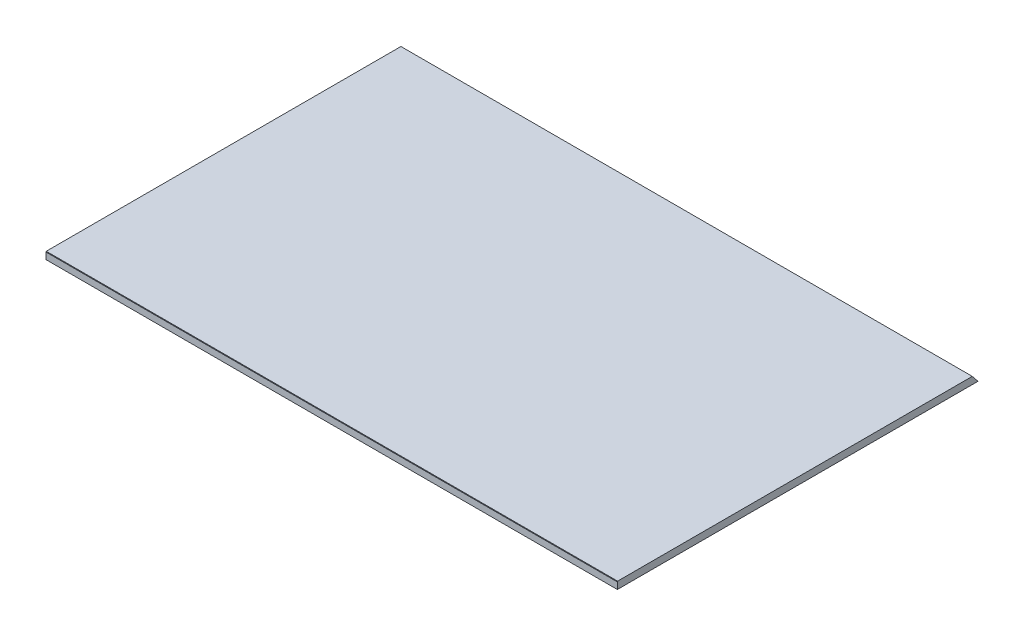
SolidWorks part; units mm, degrees
ref_plane "Front Plane" through (0, 0, 0) normal (0, 0, 1) x (1, 0, 0)
ref_plane "Top Plane" through (0, 0, 0) normal (0, 1, 0) x (1, 0, 0)
ref_plane "Right Plane" through (0, 0, 0) normal (1, 0, 0) x (0, 0, -1)
sketch "Sketch8" plane through (0, 0, 0) normal (1, 0, 0) x (0, 0, -1)
  line L3 (-88.1041, -6) -> (62.8959, -6)
  line L5 (-120, 5.68) -> (-120, 1.9989)
  line L17 (-120, 5.68) -> (-119.856, 6)
  line L25 (-120, 1.9989) -> (-106.1041, -6)
  line L26 (62.8959, -6) -> (80.8959, -3.1767)
  line L27 (-88.1041, -6) -> (-106.1041, -6)
  line L28 (80.9764, -2.9985) -> (82.7813, 0.9991)
  line L29 (80.9764, -2.9985) -> (80.8959, -3.1767)
  line L30 (78.7813, 5.9991) -> (82.7813, 0.9991)
  line L31 (-119.856, 6) -> (78.7813, 5.9991)
  point P0 (0, 0)
  point P6 (0, 0)
  dimension "D1" = 169
extrude "Boss-Extrude2" add sketch "Sketch8" along normal mid plane 320
sketch "Sketch9" plane through (0, 0, 0) normal (0, 0, 1) x (1, 0, 0)
  line L4 (0, 22.1936) -> (0, -18.3739) construction
  line L8 (-160, -6) -> (-142, -6)
  line L9 (160, -6) -> (-160, -6) construction
  line L10 (-160, 1.9989) -> (-160, -6)
  line L11 (-160, 1.9989) -> (-142, -6)
  line L12 (160, -6) -> (142, -6)
  line L13 (160, 1.9989) -> (160, -6)
  line L14 (160, 1.9989) -> (142, -6)
  dimension "D1" = 18
extrude "Cut-Extrude11" cut sketch "Sketch9" against normal through all both and the other way through all
sketch "Sketch12" plane through (0, -6, 0) normal (0, -1, 0) x (1, 0, 0)
  line L0 (-142, -62.8959) -> (-142, 106.1041) construction
  line L1 (-115, -17.8959) -> (118, -17.8959)
  line L2 (-115, -17.8959) -> (-115, -38.8959)
  line L3 (-115, -38.8959) -> (118, -38.8959)
  line L4 (118, -17.8959) -> (118, -38.8959)
  line L5 (-115, -17.8959) -> (118, -38.8959) construction
  line L6 (-115, -38.8959) -> (118, -17.8959) construction
  line L7 (142, 106.1041) -> (-142, 106.1041) construction
  point P0 (1.5, -28.3959)
  dimension "D1" = 233
  dimension "D2" = 21
  dimension "D3" = 27
  dimension "D4" = 124
extrude "Cut-Extrude12" cut sketch "Sketch12" against normal blind 2
sketch "Sketch13" plane through (0, -6, 0) normal (0, -1, 0) x (1, 0, 0)
  line L0 (142, 106.1041) -> (-142, 106.1041) construction
  line L1 (-140, 104.1041) -> (-133, 104.1041)
  line L2 (-140, 104.1041) -> (-140, 81.1041)
  line L3 (-140, 81.1041) -> (-133, 81.1041)
  line L4 (-133, 104.1041) -> (-133, 81.1041)
  line L5 (-140, 104.1041) -> (-133, 81.1041) construction
  line L6 (-140, 81.1041) -> (-133, 104.1041) construction
  line L7 (-142, -62.8959) -> (-142, 106.1041) construction
  line L8 (0, 169.9823) -> (0, -153.6761) construction
  line L13 (-188.5095, 19.0093) -> (209.6914, 19.0093) construction
  line L14 (142, -62.8959) -> (-142, -62.8959) construction
  line L15 (-140, -37.8959) -> (-133, -37.8959)
  line L16 (-140, -37.8959) -> (-140, -60.8959)
  line L17 (-140, -60.8959) -> (-133, -60.8959)
  line L18 (-133, -37.8959) -> (-133, -60.8959)
  line L19 (-140, -37.8959) -> (-133, -60.8959) construction
  line L20 (-140, -60.8959) -> (-133, -37.8959) construction
  line L21 (140, -60.8959) -> (133, -60.8959)
  line L22 (133, -37.8959) -> (133, -60.8959)
  line L23 (140, -37.8959) -> (133, -37.8959)
  line L24 (140, -37.8959) -> (140, -60.8959)
  line L25 (140, 81.1041) -> (133, 81.1041)
  line L26 (133, 104.1041) -> (133, 81.1041)
  line L27 (140, 104.1041) -> (133, 104.1041)
  line L28 (140, 104.1041) -> (140, 81.1041)
  point P0 (-136.5, 92.6041)
  point P18 (-136.5, -49.3959)
  dimension "D1" = 7
  dimension "D2" = 23
  dimension "D3" = 2
  dimension "D4" = 2
  dimension "D5" = 7
  dimension "D6" = 23
  dimension "D7" = 2
  dimension "D8" = 2
extrude "Boss-Extrude3" add sketch "Sketch13" along normal blind 2
sketch "Sketch14" plane through (-140, 0, 0) normal (-1, 0, 0) x (0, 0, 1)
  line L0 (-49.7234, -2.233) -> (-49.7234, -13.767) construction
  line L1 (-45.2234, -8) -> (-54.2234, -8)
  line L2 (-37.8959, -8) -> (-60.8959, -8) construction
  line L3 (-54.2234, -8) -> (-60.8959, -6)
  line L4 (-45.2234, -8) -> (-37.8959, -6)
  line L5 (-37.8959, -6) -> (-37.8959, -8)
  line L6 (-37.8959, -8) -> (-45.2234, -8)
  line L7 (-54.2234, -8) -> (-60.8959, -8)
  line L8 (-60.8959, -8) -> (-60.8959, -6)
  line L9 (91.8673, 0.7996) -> (91.8673, -16.5944) construction
  line L10 (87.3673, -8) -> (96.3673, -8)
  line L11 (104.1041, -8) -> (81.1041, -8) construction
  line L12 (87.3673, -8) -> (81.1041, -6)
  line L13 (96.3673, -8) -> (104.1041, -6)
  line L14 (104.1041, -6) -> (104.1041, -8)
  line L15 (104.1041, -8) -> (96.3673, -8)
  line L16 (87.3673, -8) -> (81.1041, -8)
  line L17 (81.1041, -8) -> (81.1041, -6)
  point P7 (-49.7234, -8)
  point P22 (91.8673, -8)
  line M5 (-60.8959, -6) -> (-60.8959, -8)
  line M6 (-60.8959, -8) -> (-37.8959, -8)
  dimension "D1" = 9
  dimension "D2" = 9
extrude "Cut-Extrude13" cut sketch "Sketch14" against normal through all both and the other way through all contours L3 M6 M5 | L15 L14 L13 | L17 L16 L12 | L4 L5 L6 region at (-140, -7.3333, -58.6718) region at (-140, -7.3333, 101.5251) region at (-140, -7.3333, 83.1918)
